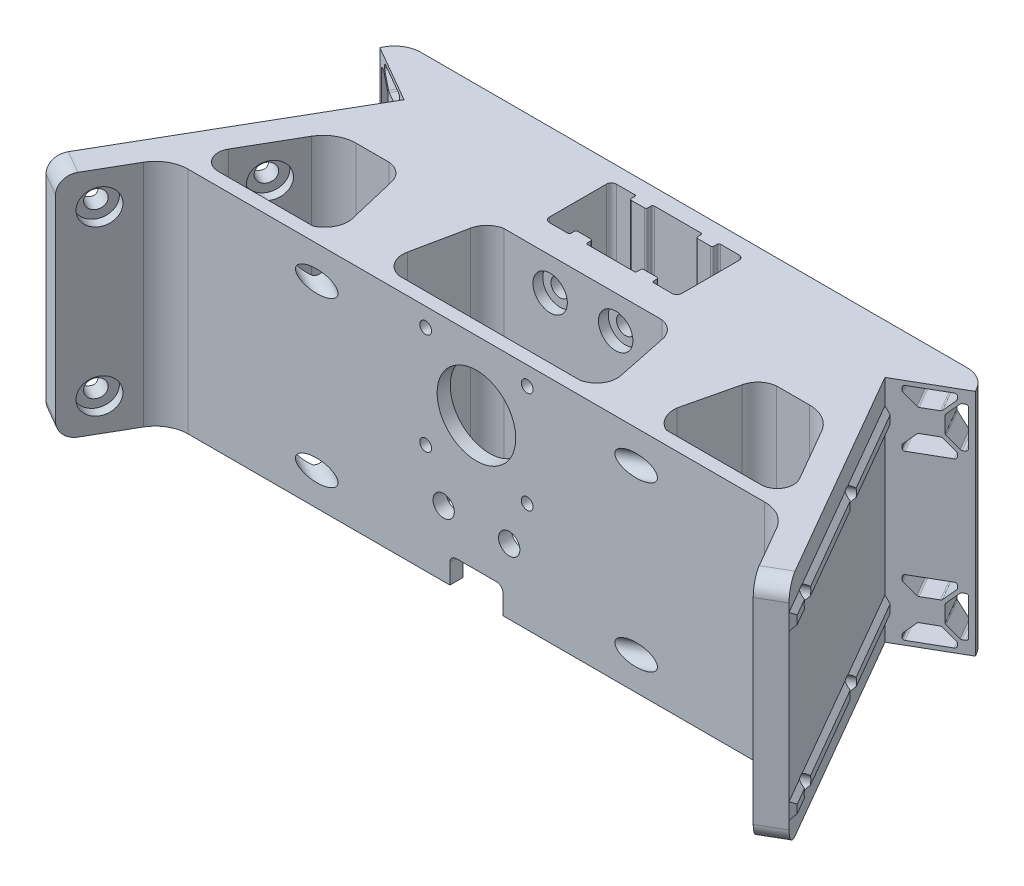
SolidWorks part; units mm, degrees
ref_plane "Front Plane" through (0, 0, 0) normal (0, 0, 1) x (1, 0, 0)
ref_plane "Top Plane" through (0, 0, 0) normal (0, 1, 0) x (1, 0, 0)
ref_plane "Right Plane" through (0, 0, 0) normal (1, 0, 0) x (0, 0, -1)
sketch "Sketch1" plane through (0, 0, 0) normal (0, 1, 0) x (1, 0, 0)
  line L0 (0, -61.4) -> (0, -111.1933) construction
  line L1 (0, 0) -> (-7.6, 0) construction
  line L2 (0, 0) -> (0, -20.4) construction
  line L3 (0, -20.4) -> (-7.1, -20.4) construction
  line L4 (-20.2, 0) -> (-20.2, -20.4) construction
  line L5 (0, 5) -> (-83.3812, 5)
  line L6 (-90.3094, 1) -> (-90.8868, 0)
  line L7 (-90.8868, 0) -> (-73.393, -10.1)
  line L8 (-73.393, -10.1) -> (-113.393, -79.382)
  line L9 (-113.393, -79.382) -> (-106.4648, -83.382)
  line L10 (-106.4648, -83.382) -> (-96.6603, -66.4)
  line L11 (-69.2361, -28.9) -> (0, -28.9)
  line L12 (0, -57.4) -> (0, -61.4)
  line L13 (0, -20.4) -> (-7.1, -20.4)
  line L14 (-20.2, -18.9) -> (-20.2, -1.5)
  line L15 (-18.7, 0) -> (-13.1, 0)
  line L16 (-82.8038, -57.4) -> (0, -57.4)
  line L17 (0, -20.4) -> (0, -28.9)
  line L18 (0, -61.4) -> (-88, -61.4)
  line L19 (-87.134, -49.9) -> (-77.8964, -33.9)
  line L20 (0, 0) -> (0, -20.4) construction
  line L21 (-7.6, -0.5) -> (-7.6, -1.5)
  line L22 (-20.2, -10.2) -> (0, -10.2) construction
  line L23 (-8.1, -2) -> (-12.1, -2)
  line L24 (-12.6, -0.5) -> (-12.6, -1.5)
  line L25 (-12.6, -19.9) -> (-12.6, -18.9)
  line L26 (-8.1, -18.4) -> (-12.1, -18.4)
  line L27 (-12.6, 0) -> (-20.2, 0) construction
  line L28 (-7.1, 0) -> (0, 0)
  line L29 (-7.6, -19.9) -> (-7.6, -18.9)
  line L30 (-13.1, -20.4) -> (-20.2, -20.4) construction
  line L31 (-13.1, -20.4) -> (-18.7, -20.4)
  line L32 (0, -28.9) -> (0, -57.4) construction
  line L33 (0, 5) -> (0, 0)
  arc A0 (-88, -61.4) -> (-96.6603, -66.4) centre (-88, -71.4) ccw
  arc A1 (-77.8964, -33.9) -> (-69.2361, -28.9) centre (-69.2361, -38.9) cw
  arc A2 (-82.8038, -57.4) -> (-87.134, -49.9) centre (-82.8038, -52.4) cw
  arc A3 (-83.3812, 5) -> (-90.3094, 1) centre (-83.3812, -3) ccw
  arc A4 (-7.1, 0) -> (-7.6, -0.5) centre (-7.1, -0.5) ccw
  arc A5 (-12.6, -0.5) -> (-13.1, 0) centre (-13.1, -0.5) ccw
  arc A6 (-7.6, -1.5) -> (-8.1, -2) centre (-8.1, -1.5) cw
  arc A7 (-12.1, -2) -> (-12.6, -1.5) centre (-12.1, -1.5) cw
  arc A8 (-20.2, -1.5) -> (-18.7, 0) centre (-18.7, -1.5) cw
  arc A9 (-18.7, -20.4) -> (-20.2, -18.9) centre (-18.7, -18.9) cw
  arc A10 (-12.1, -18.4) -> (-12.6, -18.9) centre (-12.1, -18.9) ccw
  arc A11 (-7.6, -18.9) -> (-8.1, -18.4) centre (-8.1, -18.9) ccw
  arc A12 (-12.6, -19.9) -> (-13.1, -20.4) centre (-13.1, -19.9) cw
  arc A13 (-7.1, -20.4) -> (-7.6, -19.9) centre (-7.1, -19.9) cw
  point P24 (-91.4641, -57.4)
  point P27 (-88, 5)
  point P30 (-10.1, 0)
  point P63 (-10.1, -20.4)
  dimension "D13" = 10
  dimension "D14" = 5
  dimension "D15" = 8
  dimension "D17" = 0.5
  dimension "D18" = 1.5
  dimension "D1" = 20.2
  dimension "D2" = 20.4
  dimension "D3" = 5
  dimension "D4" = 88
  dimension "D5" = 120
  dimension "D6" = 5
  dimension "D7" = 20.2
  dimension "D8" = 80
  dimension "D9" = 8
  dimension "D10" = 8.5
  dimension "D11" = 4
  dimension "D12" = 37
  dimension "D16" = 5
extrude "Boss-Extrude2" add sketch "Sketch1" along normal blind 70
sketch "Sketch2" plane through (-50.6714, 0, -29.2551) normal (-0.866, 0, -0.5) x (-0.5, 0, 0.866)
  line L0 (45.4434, 70) -> (45.4434, 0) construction
  line L1 (45.4434, 62.5) -> (125.4434, 62.5)
  line L2 (45.4434, 62.5) -> (45.4434, 57.5)
  line L3 (45.4434, 57.5) -> (125.4434, 57.5)
  line L4 (125.4434, 62.5) -> (125.4434, 57.5)
  line L5 (125.4434, 70) -> (125.4434, 0) construction
  line L6 (45.4434, 70) -> (125.4434, 70) construction
  line L7 (45.4434, 35) -> (125.4434, 35) construction
  line L8 (125.4434, 7.5) -> (125.4434, 12.5)
  line L9 (45.4434, 12.5) -> (125.4434, 12.5)
  line L10 (45.4434, 7.5) -> (45.4434, 12.5)
  line L11 (45.4434, 7.5) -> (125.4434, 7.5)
  dimension "D1" = 5
  dimension "D2" = 7.5
extrude "Boss-Extrude3" add sketch "Sketch2" along normal blind 1.5 draft 40
hole_wizard "CBORE for M5 SHCS2" positions "Sketch5" profile "Sketch4" counterbore size "M5" standard "ANSI Metric" end condition up to next
sketch "Sketch5" plane through (-43.7431, 0, -25.2551) normal (0.866, 0, 0.5) x (0.5, 0, -0.866)
  line L0 (-125.4434, 60) -> (-68.3064, 60) construction
  line L1 (-125.4434, 70) -> (-125.4434, 0) construction
  line L2 (-68.3064, 70) -> (-68.3064, 0) construction
  line L4 (-86.7817, 70) -> (-68.3064, 70) construction
  line L5 (-125.4434, 10) -> (-68.3064, 10) construction
  line L7 (-125.4434, 0) -> (-105.8342, 0) construction
  line L10 (-125.4434, 70) -> (-105.8342, 70) construction
  line L11 (-115.6388, 70) -> (-115.6388, 60) construction
  line L13 (-77.5441, 70) -> (-77.5441, 60) construction
  point P0 (-77.5441, 60)
  point P2 (-77.5441, 10)
  point P4 (-115.6388, 60)
  point P6 (-115.6388, 10)
  dimension "D1" = 10
  dimension "D2" = 10
sketch "Sketch4" plane through (-82.5152, 60, 41.9) normal (0, 1, 0) x (0.5, 0, -0.866)
  line L0 (0, 0) -> (0, 9.5)
  line L1 (0, 9.5) -> (2.75, 9.5)
  line L3 (2.75, 9.5) -> (2.75, 3)
  line L4 (2.75, 3) -> (5.25, 3)
  line L5 (5.25, 3) -> (5.25, 0)
  line L7 (5.25, 0) -> (0, 0)
  line L11 (0, -6.35) -> (0, 107.95) construction
  dimension "Thru Hole Dia." = 5.5
  dimension "Thru Hole Depth" = 9.5
  dimension "C'Bore Dia." = 10.5
  dimension "C'Bore Depth" = 3
hole_wizard "CBORE for M5 SHCS3" positions "Sketch7" profile "Sketch6" counterbore size "M5" standard "ANSI Metric" end condition up to next
sketch "Sketch7" plane through (0, 0, 28.9) normal (0, 0, 1) x (1, 0, 0)
  line L0 (0, 60) -> (0, 0) construction
  line L1 (-69.2361, 70) -> (0, 70) construction
  line L2 (-69.2361, 0) -> (0, 0) construction
  line L4 (0, 60) -> (-28.3411, 60)
  line L6 (0, 20) -> (-25.3792, 20) construction
  line L8 (-69.2361, 0) -> (0, 0) construction
  line L10 (0, 70) -> (0, 0) construction
  point P0 (-10, 20)
  point P2 (-10, 60)
  dimension "D1" = 10
  dimension "D2" = 10
  dimension "D3" = 20
sketch "Sketch6" plane through (-10, 20, 28.9) normal (1, 0, 0) x (0, -1, 0)
  line L0 (0, 0) -> (0, 10.5)
  line L1 (0, 10.5) -> (2.75, 10.5)
  line L3 (2.75, 10.5) -> (2.75, 3)
  line L4 (2.75, 3) -> (5.25, 3)
  line L5 (5.25, 3) -> (5.25, 0)
  line L7 (5.25, 0) -> (0, 0)
  line L11 (0, -6.35) -> (0, 107.95) construction
  dimension "Thru Hole Dia." = 5.5
  dimension "Thru Hole Depth" = 10.5
  dimension "C'Bore Dia." = 10.5
  dimension "C'Bore Depth" = 3
chamfer "Chamfer1" [suppressed] distance 5 angle 45
chamfer "Chamfer2" [suppressed] distance 5 angle 45
fillet "Fillet1" radius 5 2 edges at (-109.9289, 0, 81.382) (-109.9289, 70, 81.382)
sketch "Sketch14" plane through (-22.7217, 0, 39.3551) normal (-0.5, 0, 0.866) x (0.866, 0, 0.5)
  line L0 (-73.9972, 68.5) -> (-63.0232, 68.5)
  line L1 (-62.5152, 67.992) -> (-62.5152, 67.2661)
  line L2 (-65.7671, 63.8038) -> (-62.664, 66.9069)
  line L3 (-66.1263, 63.655) -> (-70.8942, 63.655)
  line L12 (-74.5052, 67.992) -> (-74.5052, 67.2661)
  line L13 (-74.3564, 66.9069) -> (-71.2534, 63.8038)
  line L14 (-77.0102, 65.487) -> (-77.0102, 54.513)
  line L15 (-76.5022, 54.005) -> (-75.7763, 54.005)
  line L16 (-75.4171, 54.1538) -> (-72.314, 57.2569)
  line L17 (-72.1652, 57.6161) -> (-72.1652, 62.3839)
  line L18 (-72.314, 62.7431) -> (-75.4171, 65.8462)
  line L19 (-75.7763, 65.995) -> (-76.5022, 65.995)
  line L20 (-73.9972, 51.5) -> (-63.0232, 51.5)
  line L21 (-62.5152, 52.008) -> (-62.5152, 52.7339)
  line L22 (-62.664, 53.0931) -> (-65.7671, 56.1962)
  line L23 (-66.1263, 56.345) -> (-70.8942, 56.345)
  line L25 (-71.2534, 56.1962) -> (-74.3564, 53.0931)
  line L26 (-74.5052, 52.7339) -> (-74.5052, 52.008)
  line L52 (-74.5052, 52.008) -> (-74.5052, 52.7339)
  line L53 (-71.6482, 51.5) -> (-73.9972, 51.5)
  line L54 (-71.1402, 50.508) -> (-71.1402, 50.992)
  line L55 (-77.0102, 50) -> (-71.6482, 50)
  line L56 (-78.5102, 56.862) -> (-78.5102, 51.5)
  line L57 (-77.5182, 57.37) -> (-78.0022, 57.37)
  line L58 (-77.0102, 54.513) -> (-77.0102, 56.862)
  line L59 (-75.7763, 54.005) -> (-76.5022, 54.005)
  line L60 (-72.314, 57.2569) -> (-75.4171, 54.1538)
  line L61 (-72.1652, 62.3839) -> (-72.1652, 57.6161)
  line L62 (-75.4171, 65.8462) -> (-72.314, 62.7431)
  line L63 (-76.5022, 65.995) -> (-75.7763, 65.995)
  line L64 (-77.0102, 63.138) -> (-77.0102, 65.487)
  line L65 (-78.0022, 62.63) -> (-77.5182, 62.63)
  line L66 (-78.5102, 68.5) -> (-78.5102, 63.138)
  line L67 (-71.6482, 70) -> (-77.0102, 70)
  line L68 (-71.1402, 69.008) -> (-71.1402, 69.492)
  line L69 (-73.9972, 68.5) -> (-71.6482, 68.5)
  line L70 (-74.5052, 67.2661) -> (-74.5052, 67.992)
  line L71 (-71.2534, 63.8038) -> (-74.3564, 66.9069)
  line L72 (-66.1263, 63.655) -> (-70.8942, 63.655)
  line L73 (-62.664, 66.9069) -> (-65.7671, 63.8038)
  line L74 (-62.5152, 67.992) -> (-62.5152, 67.2661)
  line L75 (-65.3722, 68.5) -> (-63.0232, 68.5)
  line L76 (-65.8802, 69.492) -> (-65.8802, 69.008)
  line L77 (-60.0102, 70) -> (-65.3722, 70)
  line L78 (-58.5102, 63.138) -> (-58.5102, 68.5)
  line L79 (-59.5022, 62.63) -> (-59.0182, 62.63)
  line L80 (-60.0102, 65.487) -> (-60.0102, 63.138)
  line L81 (-61.2442, 65.995) -> (-60.5182, 65.995)
  line L82 (-64.7064, 62.7431) -> (-61.6034, 65.8462)
  line L83 (-64.8552, 57.6161) -> (-64.8552, 62.3839)
  line L84 (-61.6034, 54.1538) -> (-64.7064, 57.2569)
  line L85 (-60.5182, 54.005) -> (-61.2442, 54.005)
  line L86 (-60.0102, 56.862) -> (-60.0102, 54.513)
  line L87 (-59.0182, 57.37) -> (-59.5022, 57.37)
  line L88 (-58.5102, 51.5) -> (-58.5102, 56.862)
  line L89 (-65.3722, 50) -> (-60.0102, 50)
  line L90 (-65.8802, 50.992) -> (-65.8802, 50.508)
  line L91 (-63.0232, 51.5) -> (-65.3722, 51.5)
  line L92 (-62.5152, 52.7339) -> (-62.5152, 52.008)
  line L93 (-65.7671, 56.1962) -> (-62.664, 53.0931)
  line L94 (-70.8942, 56.345) -> (-66.1263, 56.345)
  line L95 (-74.3564, 53.0931) -> (-71.2534, 56.1962)
  line L96 (-74.5052, 52.008) -> (-74.5052, 52.7339) construction
  line L97 (-71.6482, 51.5) -> (-73.9972, 51.5) construction
  line L98 (-71.1402, 50.508) -> (-71.1402, 50.992) construction
  line L99 (-77.0102, 50) -> (-71.6482, 50) construction
  line L100 (-78.5102, 56.862) -> (-78.5102, 51.5) construction
  line L101 (-77.5182, 57.37) -> (-78.0022, 57.37) construction
  line L102 (-77.0102, 54.513) -> (-77.0102, 56.862) construction
  line L103 (-75.7763, 54.005) -> (-76.5022, 54.005) construction
  line L104 (-72.314, 57.2569) -> (-75.4171, 54.1538) construction
  line L105 (-72.1652, 62.3839) -> (-72.1652, 57.6161) construction
  line L106 (-75.4171, 65.8462) -> (-72.314, 62.7431) construction
  line L107 (-76.5022, 65.995) -> (-75.7763, 65.995) construction
  line L108 (-77.0102, 63.138) -> (-77.0102, 65.487) construction
  line L109 (-78.0022, 62.63) -> (-77.5182, 62.63) construction
  line L110 (-78.5102, 68.5) -> (-78.5102, 63.138) construction
  line L111 (-71.6482, 70) -> (-77.0102, 70) construction
  line L112 (-71.1402, 69.008) -> (-71.1402, 69.492) construction
  line L113 (-73.9972, 68.5) -> (-71.6482, 68.5) construction
  line L114 (-74.5052, 67.2661) -> (-74.5052, 67.992) construction
  line L115 (-71.2534, 63.8038) -> (-74.3564, 66.9069) construction
  line L116 (-66.1263, 63.655) -> (-70.8942, 63.655) construction
  line L117 (-62.664, 66.9069) -> (-65.7671, 63.8038) construction
  line L118 (-62.5152, 67.992) -> (-62.5152, 67.2661) construction
  line L119 (-65.3722, 68.5) -> (-63.0232, 68.5) construction
  line L120 (-65.8802, 69.492) -> (-65.8802, 69.008) construction
  line L121 (-60.0102, 70) -> (-65.3722, 70) construction
  line L122 (-58.5102, 63.138) -> (-58.5102, 68.5) construction
  line L123 (-59.5022, 62.63) -> (-59.0182, 62.63) construction
  line L124 (-60.0102, 65.487) -> (-60.0102, 63.138) construction
  line L125 (-61.2442, 65.995) -> (-60.5182, 65.995) construction
  line L126 (-64.7064, 62.7431) -> (-61.6034, 65.8462) construction
  line L127 (-64.8552, 57.6161) -> (-64.8552, 62.3839) construction
  line L128 (-61.6034, 54.1538) -> (-64.7064, 57.2569) construction
  line L129 (-60.5182, 54.005) -> (-61.2442, 54.005) construction
  line L130 (-60.0102, 56.862) -> (-60.0102, 54.513) construction
  line L131 (-59.0182, 57.37) -> (-59.5022, 57.37) construction
  line L132 (-58.5102, 51.5) -> (-58.5102, 56.862) construction
  line L133 (-65.3722, 50) -> (-60.0102, 50) construction
  line L134 (-65.8802, 50.992) -> (-65.8802, 50.508) construction
  line L135 (-63.0232, 51.5) -> (-65.3722, 51.5) construction
  line L136 (-62.5152, 52.7339) -> (-62.5152, 52.008) construction
  line L137 (-65.7671, 56.1962) -> (-62.664, 53.0931) construction
  line L138 (-70.8942, 56.345) -> (-66.1263, 56.345) construction
  line L139 (-74.3564, 53.0931) -> (-71.2534, 56.1962) construction
  arc A0 (-74.5052, 67.992) -> (-73.9972, 68.5) centre (-73.9972, 67.992) cw
  arc A1 (-74.3564, 66.9069) -> (-74.5052, 67.2661) centre (-73.9972, 67.2661) cw
  arc A2 (-71.2534, 63.8038) -> (-70.8942, 63.655) centre (-70.8942, 64.163) ccw
  arc A3 (-66.1263, 63.655) -> (-65.7671, 63.8038) centre (-66.1263, 64.163) ccw
  arc A4 (-62.664, 66.9069) -> (-62.5152, 67.2661) centre (-63.0232, 67.2661) ccw
  arc A5 (-62.5152, 67.992) -> (-63.0232, 68.5) centre (-63.0232, 67.992) ccw
  arc A6 (-77.0102, 54.513) -> (-76.5022, 54.005) centre (-76.5022, 54.513) ccw
  arc A7 (-75.7763, 54.005) -> (-75.4171, 54.1538) centre (-75.7763, 54.513) ccw
  arc A8 (-72.314, 57.2569) -> (-72.1652, 57.6161) centre (-72.6732, 57.6161) ccw
  arc A9 (-72.1652, 62.3839) -> (-72.314, 62.7431) centre (-72.6732, 62.3839) ccw
  arc A10 (-75.4171, 65.8462) -> (-75.7763, 65.995) centre (-75.7763, 65.487) ccw
  arc A11 (-76.5022, 65.995) -> (-77.0102, 65.487) centre (-76.5022, 65.487) ccw
  arc A36 (-63.0232, 51.5) -> (-62.5152, 52.008) centre (-63.0232, 52.008) ccw
  arc A37 (-62.5152, 52.7339) -> (-62.664, 53.0931) centre (-63.0232, 52.7339) ccw
  arc A38 (-65.7671, 56.1962) -> (-66.1263, 56.345) centre (-66.1263, 55.837) ccw
  arc A39 (-74.3564, 53.0931) -> (-74.5052, 52.7339) centre (-73.9972, 52.7339) ccw
  arc A40 (-74.5052, 52.008) -> (-73.9972, 51.5) centre (-73.9972, 52.008) ccw
  arc A41 (-70.8942, 56.345) -> (-71.2534, 56.1962) centre (-70.8942, 55.837) ccw
  arc A68 (-74.5052, 52.008) -> (-73.9972, 51.5) centre (-73.9972, 52.008) ccw
  arc A69 (-71.1402, 50.992) -> (-71.6482, 51.5) centre (-71.6482, 50.992) ccw
  arc A70 (-71.6482, 50) -> (-71.1402, 50.508) centre (-71.6482, 50.508) ccw
  arc A71 (-78.5102, 51.5) -> (-77.0102, 50) centre (-77.0102, 51.5) ccw
  arc A72 (-78.0022, 57.37) -> (-78.5102, 56.862) centre (-78.0022, 56.862) ccw
  arc A73 (-77.0102, 56.862) -> (-77.5182, 57.37) centre (-77.5182, 56.862) ccw
  arc A74 (-77.0102, 54.513) -> (-76.5022, 54.005) centre (-76.5022, 54.513) ccw
  arc A75 (-75.7763, 54.005) -> (-75.4171, 54.1538) centre (-75.7763, 54.513) ccw
  arc A76 (-72.314, 57.2569) -> (-72.1652, 57.6161) centre (-72.6732, 57.6161) ccw
  arc A77 (-72.1652, 62.3839) -> (-72.314, 62.7431) centre (-72.6732, 62.3839) ccw
  arc A78 (-75.4171, 65.8462) -> (-75.7763, 65.995) centre (-75.7763, 65.487) ccw
  arc A79 (-76.5022, 65.995) -> (-77.0102, 65.487) centre (-76.5022, 65.487) ccw
  arc A80 (-77.5182, 62.63) -> (-77.0102, 63.138) centre (-77.5182, 63.138) ccw
  arc A81 (-78.5102, 63.138) -> (-78.0022, 62.63) centre (-78.0022, 63.138) ccw
  arc A82 (-77.0102, 70) -> (-78.5102, 68.5) centre (-77.0102, 68.5) ccw
  arc A83 (-71.1402, 69.492) -> (-71.6482, 70) centre (-71.6482, 69.492) ccw
  arc A84 (-71.6482, 68.5) -> (-71.1402, 69.008) centre (-71.6482, 69.008) ccw
  arc A85 (-73.9972, 68.5) -> (-74.5052, 67.992) centre (-73.9972, 67.992) ccw
  arc A86 (-74.5052, 67.2661) -> (-74.3564, 66.9069) centre (-73.9972, 67.2661) ccw
  arc A87 (-71.2534, 63.8038) -> (-70.8942, 63.655) centre (-70.8942, 64.163) ccw
  arc A88 (-66.1263, 63.655) -> (-65.7671, 63.8038) centre (-66.1263, 64.163) ccw
  arc A89 (-62.664, 66.9069) -> (-62.5152, 67.2661) centre (-63.0232, 67.2661) ccw
  arc A90 (-62.5152, 67.992) -> (-63.0232, 68.5) centre (-63.0232, 67.992) ccw
  arc A91 (-65.8802, 69.008) -> (-65.3722, 68.5) centre (-65.3722, 69.008) ccw
  arc A92 (-65.3722, 70) -> (-65.8802, 69.492) centre (-65.3722, 69.492) ccw
  arc A93 (-58.5102, 68.5) -> (-60.0102, 70) centre (-60.0102, 68.5) ccw
  arc A94 (-59.0182, 62.63) -> (-58.5102, 63.138) centre (-59.0182, 63.138) ccw
  arc A95 (-60.0102, 63.138) -> (-59.5022, 62.63) centre (-59.5022, 63.138) ccw
  arc A96 (-60.0102, 65.487) -> (-60.5182, 65.995) centre (-60.5182, 65.487) ccw
  arc A97 (-61.2442, 65.995) -> (-61.6034, 65.8462) centre (-61.2442, 65.487) ccw
  arc A98 (-64.7064, 62.7431) -> (-64.8552, 62.3839) centre (-64.3472, 62.3839) ccw
  arc A99 (-64.8552, 57.6161) -> (-64.7064, 57.2569) centre (-64.3472, 57.6161) ccw
  arc A100 (-61.6034, 54.1538) -> (-61.2442, 54.005) centre (-61.2442, 54.513) ccw
  arc A101 (-60.5182, 54.005) -> (-60.0102, 54.513) centre (-60.5182, 54.513) ccw
  arc A102 (-59.5022, 57.37) -> (-60.0102, 56.862) centre (-59.5022, 56.862) ccw
  arc A103 (-58.5102, 56.862) -> (-59.0182, 57.37) centre (-59.0182, 56.862) ccw
  arc A104 (-60.0102, 50) -> (-58.5102, 51.5) centre (-60.0102, 51.5) ccw
  arc A105 (-65.8802, 50.508) -> (-65.3722, 50) centre (-65.3722, 50.508) ccw
  arc A106 (-65.3722, 51.5) -> (-65.8802, 50.992) centre (-65.3722, 50.992) ccw
  arc A107 (-63.0232, 51.5) -> (-62.5152, 52.008) centre (-63.0232, 52.008) ccw
  arc A108 (-62.5152, 52.7339) -> (-62.664, 53.0931) centre (-63.0232, 52.7339) ccw
  arc A109 (-65.7671, 56.1962) -> (-66.1263, 56.345) centre (-66.1263, 55.837) ccw
  arc A110 (-70.8942, 56.345) -> (-71.2534, 56.1962) centre (-70.8942, 55.837) ccw
  arc A111 (-74.3564, 53.0931) -> (-74.5052, 52.7339) centre (-73.9972, 52.7339) ccw
  arc A112 (-74.5052, 52.008) -> (-73.9972, 51.5) centre (-73.9972, 52.008) ccw construction
  arc A113 (-71.1402, 50.992) -> (-71.6482, 51.5) centre (-71.6482, 50.992) ccw construction
  arc A114 (-71.6482, 50) -> (-71.1402, 50.508) centre (-71.6482, 50.508) ccw construction
  arc A115 (-78.5102, 51.5) -> (-77.0102, 50) centre (-77.0102, 51.5) ccw construction
  arc A116 (-78.0022, 57.37) -> (-78.5102, 56.862) centre (-78.0022, 56.862) ccw construction
  arc A117 (-77.0102, 56.862) -> (-77.5182, 57.37) centre (-77.5182, 56.862) ccw construction
  arc A118 (-77.0102, 54.513) -> (-76.5022, 54.005) centre (-76.5022, 54.513) ccw construction
  arc A119 (-75.7763, 54.005) -> (-75.4171, 54.1538) centre (-75.7763, 54.513) ccw construction
  arc A120 (-72.314, 57.2569) -> (-72.1652, 57.6161) centre (-72.6732, 57.6161) ccw construction
  arc A121 (-72.1652, 62.3839) -> (-72.314, 62.7431) centre (-72.6732, 62.3839) ccw construction
  arc A122 (-75.4171, 65.8462) -> (-75.7763, 65.995) centre (-75.7763, 65.487) ccw construction
  arc A123 (-76.5022, 65.995) -> (-77.0102, 65.487) centre (-76.5022, 65.487) ccw construction
  arc A124 (-77.5182, 62.63) -> (-77.0102, 63.138) centre (-77.5182, 63.138) ccw construction
  arc A125 (-78.5102, 63.138) -> (-78.0022, 62.63) centre (-78.0022, 63.138) ccw construction
  arc A126 (-77.0102, 70) -> (-78.5102, 68.5) centre (-77.0102, 68.5) ccw construction
  arc A127 (-71.1402, 69.492) -> (-71.6482, 70) centre (-71.6482, 69.492) ccw construction
  arc A128 (-71.6482, 68.5) -> (-71.1402, 69.008) centre (-71.6482, 69.008) ccw construction
  arc A129 (-73.9972, 68.5) -> (-74.5052, 67.992) centre (-73.9972, 67.992) ccw construction
  arc A130 (-74.5052, 67.2661) -> (-74.3564, 66.9069) centre (-73.9972, 67.2661) ccw construction
  arc A131 (-71.2534, 63.8038) -> (-70.8942, 63.655) centre (-70.8942, 64.163) ccw construction
  arc A132 (-66.1263, 63.655) -> (-65.7671, 63.8038) centre (-66.1263, 64.163) ccw construction
  arc A133 (-62.664, 66.9069) -> (-62.5152, 67.2661) centre (-63.0232, 67.2661) ccw construction
  arc A134 (-62.5152, 67.992) -> (-63.0232, 68.5) centre (-63.0232, 67.992) ccw construction
  arc A135 (-65.8802, 69.008) -> (-65.3722, 68.5) centre (-65.3722, 69.008) ccw construction
  arc A136 (-65.3722, 70) -> (-65.8802, 69.492) centre (-65.3722, 69.492) ccw construction
  arc A137 (-58.5102, 68.5) -> (-60.0102, 70) centre (-60.0102, 68.5) ccw construction
  arc A138 (-59.0182, 62.63) -> (-58.5102, 63.138) centre (-59.0182, 63.138) ccw construction
  arc A139 (-60.0102, 63.138) -> (-59.5022, 62.63) centre (-59.5022, 63.138) ccw construction
  arc A140 (-60.0102, 65.487) -> (-60.5182, 65.995) centre (-60.5182, 65.487) ccw construction
  arc A141 (-61.2442, 65.995) -> (-61.6034, 65.8462) centre (-61.2442, 65.487) ccw construction
  arc A142 (-64.7064, 62.7431) -> (-64.8552, 62.3839) centre (-64.3472, 62.3839) ccw construction
  arc A143 (-64.8552, 57.6161) -> (-64.7064, 57.2569) centre (-64.3472, 57.6161) ccw construction
  arc A144 (-61.6034, 54.1538) -> (-61.2442, 54.005) centre (-61.2442, 54.513) ccw construction
  arc A145 (-60.5182, 54.005) -> (-60.0102, 54.513) centre (-60.5182, 54.513) ccw construction
  arc A146 (-59.5022, 57.37) -> (-60.0102, 56.862) centre (-59.5022, 56.862) ccw construction
  arc A147 (-58.5102, 56.862) -> (-59.0182, 57.37) centre (-59.0182, 56.862) ccw construction
  arc A148 (-60.0102, 50) -> (-58.5102, 51.5) centre (-60.0102, 51.5) ccw construction
  arc A149 (-65.8802, 50.508) -> (-65.3722, 50) centre (-65.3722, 50.508) ccw construction
  arc A150 (-65.3722, 51.5) -> (-65.8802, 50.992) centre (-65.3722, 50.992) ccw construction
  arc A151 (-63.0232, 51.5) -> (-62.5152, 52.008) centre (-63.0232, 52.008) ccw construction
  arc A152 (-62.5152, 52.7339) -> (-62.664, 53.0931) centre (-63.0232, 52.7339) ccw construction
  arc A153 (-65.7671, 56.1962) -> (-66.1263, 56.345) centre (-66.1263, 55.837) ccw construction
  arc A154 (-70.8942, 56.345) -> (-71.2534, 56.1962) centre (-70.8942, 55.837) ccw construction
  arc A155 (-74.3564, 53.0931) -> (-74.5052, 52.7339) centre (-73.9972, 52.7339) ccw construction
  dimension "D2" = 0
sketch "Sketch15" plane through (-22.7217, 0, 39.3551) normal (-0.5, 0, 0.866) x (0.866, 0, 0.5)
  line L0 (-77.2102, 65.487) -> (-77.2102, 54.513)
  line L1 (-76.5022, 53.805) -> (-75.7763, 53.805)
  line L2 (-75.2757, 54.0124) -> (-72.1726, 57.1154)
  line L3 (-71.9652, 57.6161) -> (-71.9652, 62.3839)
  line L4 (-72.1726, 62.8846) -> (-75.2757, 65.9876)
  line L5 (-75.7763, 66.195) -> (-76.5022, 66.195)
  line L6 (-77.0102, 65.487) -> (-77.0102, 54.513)
  line L7 (-76.5022, 54.005) -> (-75.7763, 54.005)
  line L8 (-75.4171, 54.1538) -> (-72.314, 57.2569)
  line L9 (-72.1652, 57.6161) -> (-72.1652, 62.3839)
  line L10 (-72.314, 62.7431) -> (-75.4171, 65.8462)
  line L11 (-75.7763, 65.995) -> (-76.5022, 65.995)
  line L12 (-77.0102, 65.487) -> (-77.0102, 54.513) construction
  line L13 (-76.5022, 54.005) -> (-75.7763, 54.005) construction
  line L14 (-75.4171, 54.1538) -> (-72.314, 57.2569) construction
  line L15 (-72.1652, 57.6161) -> (-72.1652, 62.3839) construction
  line L16 (-72.314, 62.7431) -> (-75.4171, 65.8462) construction
  line L17 (-75.7763, 65.995) -> (-76.5022, 65.995) construction
  line L18 (-63.0232, 68.5) -> (-73.9972, 68.5)
  line L19 (-74.5052, 67.992) -> (-74.5052, 67.2661)
  line L20 (-74.3564, 66.9069) -> (-71.2534, 63.8038)
  line L21 (-70.8942, 63.655) -> (-66.1263, 63.655)
  line L22 (-65.7671, 63.8038) -> (-62.664, 66.9069)
  line L23 (-62.5152, 67.2661) -> (-62.5152, 67.992)
  line L24 (-63.0232, 68.5) -> (-73.9972, 68.5) construction
  line L25 (-74.5052, 67.992) -> (-74.5052, 67.2661) construction
  line L26 (-74.3564, 66.9069) -> (-71.2534, 63.8038) construction
  line L27 (-70.8942, 63.655) -> (-66.1263, 63.655) construction
  line L28 (-65.7671, 63.8038) -> (-62.664, 66.9069) construction
  line L29 (-62.5152, 67.2661) -> (-62.5152, 67.992) construction
  line L30 (-73.9972, 51.5) -> (-63.0232, 51.5)
  line L31 (-74.5052, 52.7339) -> (-74.5052, 52.008)
  line L32 (-71.2534, 56.1962) -> (-74.3564, 53.0931)
  line L33 (-66.1263, 56.345) -> (-70.8942, 56.345)
  line L34 (-62.664, 53.0931) -> (-65.7671, 56.1962)
  line L35 (-62.5152, 52.008) -> (-62.5152, 52.7339)
  line L36 (-73.9972, 51.5) -> (-63.0232, 51.5) construction
  line L37 (-74.5052, 52.7339) -> (-74.5052, 52.008) construction
  line L38 (-71.2534, 56.1962) -> (-74.3564, 53.0931) construction
  line L39 (-66.1263, 56.345) -> (-70.8942, 56.345) construction
  line L40 (-62.664, 53.0931) -> (-65.7671, 56.1962) construction
  line L41 (-62.5152, 52.008) -> (-62.5152, 52.7339) construction
  line L42 (-63.0232, 68.7) -> (-73.9972, 68.7)
  line L43 (-74.7052, 67.992) -> (-74.7052, 67.2661)
  line L44 (-74.4979, 66.7654) -> (-71.3948, 63.6624)
  line L45 (-70.8942, 63.455) -> (-66.1263, 63.455)
  line L46 (-65.6257, 63.6624) -> (-62.5226, 66.7654)
  line L47 (-62.3152, 67.2661) -> (-62.3152, 67.992)
  line L48 (-73.9972, 51.3) -> (-63.0232, 51.3)
  line L49 (-62.3152, 52.008) -> (-62.3152, 52.7339)
  line L50 (-62.5226, 53.2346) -> (-65.6257, 56.3376)
  line L51 (-66.1263, 56.545) -> (-70.8942, 56.545)
  line L52 (-71.3948, 56.3376) -> (-74.4979, 53.2346)
  line L53 (-74.7052, 52.7339) -> (-74.7052, 52.008)
  line L54 (-58.5102, 35) -> (-78.7102, 35) construction
  line L55 (-58.5102, 57.5) -> (-58.5102, 12.5) construction
  line L56 (-78.7102, 70) -> (-78.7102, 0) construction
  line L57 (-62.5152, 17.992) -> (-62.5152, 17.2661) construction
  line L58 (-62.664, 16.9069) -> (-65.7671, 13.8038) construction
  line L59 (-66.1263, 13.655) -> (-70.8942, 13.655) construction
  line L60 (-71.2534, 13.8038) -> (-74.3564, 16.9069) construction
  line L61 (-74.5052, 17.2661) -> (-74.5052, 17.992) construction
  line L62 (-73.9972, 18.5) -> (-63.0232, 18.5) construction
  line L63 (-62.5152, 2.7339) -> (-62.5152, 2.008) construction
  line L64 (-65.7671, 6.1962) -> (-62.664, 3.0931) construction
  line L65 (-70.8942, 6.345) -> (-66.1263, 6.345) construction
  line L66 (-74.3564, 3.0931) -> (-71.2534, 6.1962) construction
  line L67 (-74.5052, 2.008) -> (-74.5052, 2.7339) construction
  line L68 (-63.0232, 1.5) -> (-73.9972, 1.5) construction
  line L69 (-75.7763, 4.005) -> (-76.5022, 4.005) construction
  line L70 (-72.314, 7.2569) -> (-75.4171, 4.1538) construction
  line L71 (-72.1652, 12.3839) -> (-72.1652, 7.6161) construction
  line L72 (-75.4171, 15.8462) -> (-72.314, 12.7431) construction
  line L73 (-76.5022, 15.995) -> (-75.7763, 15.995) construction
  line L74 (-77.0102, 4.513) -> (-77.0102, 15.487) construction
  line L75 (-74.7052, 17.2661) -> (-74.7052, 17.992)
  line L76 (-71.3948, 13.6624) -> (-74.4979, 16.7654)
  line L77 (-66.1263, 13.455) -> (-70.8942, 13.455)
  line L78 (-62.5226, 16.7654) -> (-65.6257, 13.6624)
  line L79 (-62.3152, 17.992) -> (-62.3152, 17.2661)
  line L80 (-73.9972, 18.7) -> (-63.0232, 18.7)
  line L81 (-62.3152, 2.7339) -> (-62.3152, 2.008)
  line L82 (-65.6257, 6.3376) -> (-62.5226, 3.2346)
  line L83 (-70.8942, 6.545) -> (-66.1263, 6.545)
  line L84 (-74.4979, 3.2346) -> (-71.3948, 6.3376)
  line L85 (-74.7052, 2.008) -> (-74.7052, 2.7339)
  line L86 (-63.0232, 1.3) -> (-73.9972, 1.3)
  line L87 (-75.7763, 3.805) -> (-76.5022, 3.805)
  line L88 (-72.1726, 7.1154) -> (-75.2757, 4.0124)
  line L89 (-71.9652, 12.3839) -> (-71.9652, 7.6161)
  line L90 (-75.2757, 15.9876) -> (-72.1726, 12.8846)
  line L91 (-76.5022, 16.195) -> (-75.7763, 16.195)
  line L92 (-77.2102, 4.513) -> (-77.2102, 15.487)
  arc A0 (-77.2102, 54.513) -> (-76.5022, 53.805) centre (-76.5022, 54.513) ccw
  arc A1 (-75.7763, 53.805) -> (-75.2757, 54.0124) centre (-75.7763, 54.513) ccw
  arc A2 (-72.1726, 57.1154) -> (-71.9652, 57.6161) centre (-72.6732, 57.6161) ccw
  arc A3 (-71.9652, 62.3839) -> (-72.1726, 62.8846) centre (-72.6732, 62.3839) ccw
  arc A4 (-75.2757, 65.9876) -> (-75.7763, 66.195) centre (-75.7763, 65.487) ccw
  arc A5 (-76.5022, 66.195) -> (-77.2102, 65.487) centre (-76.5022, 65.487) ccw
  arc A6 (-77.0102, 54.513) -> (-76.5022, 54.005) centre (-76.5022, 54.513) ccw
  arc A7 (-75.7763, 54.005) -> (-75.4171, 54.1538) centre (-75.7763, 54.513) ccw
  arc A8 (-72.314, 57.2569) -> (-72.1652, 57.6161) centre (-72.6732, 57.6161) ccw
  arc A9 (-72.1652, 62.3839) -> (-72.314, 62.7431) centre (-72.6732, 62.3839) ccw
  arc A10 (-75.4171, 65.8462) -> (-75.7763, 65.995) centre (-75.7763, 65.487) ccw
  arc A11 (-76.5022, 65.995) -> (-77.0102, 65.487) centre (-76.5022, 65.487) ccw
  arc A12 (-77.0102, 54.513) -> (-76.5022, 54.005) centre (-76.5022, 54.513) ccw construction
  arc A13 (-75.7763, 54.005) -> (-75.4171, 54.1538) centre (-75.7763, 54.513) ccw construction
  arc A14 (-72.314, 57.2569) -> (-72.1652, 57.6161) centre (-72.6732, 57.6161) ccw construction
  arc A15 (-72.1652, 62.3839) -> (-72.314, 62.7431) centre (-72.6732, 62.3839) ccw construction
  arc A16 (-75.4171, 65.8462) -> (-75.7763, 65.995) centre (-75.7763, 65.487) ccw construction
  arc A17 (-76.5022, 65.995) -> (-77.0102, 65.487) centre (-76.5022, 65.487) ccw construction
  arc A18 (-73.9972, 68.5) -> (-74.5052, 67.992) centre (-73.9972, 67.992) ccw
  arc A19 (-74.5052, 67.2661) -> (-74.3564, 66.9069) centre (-73.9972, 67.2661) ccw
  arc A20 (-71.2534, 63.8038) -> (-70.8942, 63.655) centre (-70.8942, 64.163) ccw
  arc A21 (-66.1263, 63.655) -> (-65.7671, 63.8038) centre (-66.1263, 64.163) ccw
  arc A22 (-62.664, 66.9069) -> (-62.5152, 67.2661) centre (-63.0232, 67.2661) ccw
  arc A23 (-62.5152, 67.992) -> (-63.0232, 68.5) centre (-63.0232, 67.992) ccw
  arc A24 (-73.9972, 68.5) -> (-74.5052, 67.992) centre (-73.9972, 67.992) ccw construction
  arc A25 (-74.5052, 67.2661) -> (-74.3564, 66.9069) centre (-73.9972, 67.2661) ccw construction
  arc A26 (-71.2534, 63.8038) -> (-70.8942, 63.655) centre (-70.8942, 64.163) ccw construction
  arc A27 (-66.1263, 63.655) -> (-65.7671, 63.8038) centre (-66.1263, 64.163) ccw construction
  arc A28 (-62.664, 66.9069) -> (-62.5152, 67.2661) centre (-63.0232, 67.2661) ccw construction
  arc A29 (-62.5152, 67.992) -> (-63.0232, 68.5) centre (-63.0232, 67.992) ccw construction
  arc A30 (-74.5052, 52.008) -> (-73.9972, 51.5) centre (-73.9972, 52.008) ccw
  arc A31 (-74.3564, 53.0931) -> (-74.5052, 52.7339) centre (-73.9972, 52.7339) ccw
  arc A32 (-70.8942, 56.345) -> (-71.2534, 56.1962) centre (-70.8942, 55.837) ccw
  arc A33 (-65.7671, 56.1962) -> (-66.1263, 56.345) centre (-66.1263, 55.837) ccw
  arc A34 (-62.5152, 52.7339) -> (-62.664, 53.0931) centre (-63.0232, 52.7339) ccw
  arc A35 (-63.0232, 51.5) -> (-62.5152, 52.008) centre (-63.0232, 52.008) ccw
  arc A36 (-74.5052, 52.008) -> (-73.9972, 51.5) centre (-73.9972, 52.008) ccw construction
  arc A37 (-74.3564, 53.0931) -> (-74.5052, 52.7339) centre (-73.9972, 52.7339) ccw construction
  arc A38 (-70.8942, 56.345) -> (-71.2534, 56.1962) centre (-70.8942, 55.837) ccw construction
  arc A39 (-65.7671, 56.1962) -> (-66.1263, 56.345) centre (-66.1263, 55.837) ccw construction
  arc A40 (-62.5152, 52.7339) -> (-62.664, 53.0931) centre (-63.0232, 52.7339) ccw construction
  arc A41 (-63.0232, 51.5) -> (-62.5152, 52.008) centre (-63.0232, 52.008) ccw construction
  arc A42 (-73.9972, 68.7) -> (-74.7052, 67.992) centre (-73.9972, 67.992) ccw
  arc A43 (-74.7052, 67.2661) -> (-74.4979, 66.7654) centre (-73.9972, 67.2661) ccw
  arc A44 (-71.3948, 63.6624) -> (-70.8942, 63.455) centre (-70.8942, 64.163) ccw
  arc A45 (-66.1263, 63.455) -> (-65.6257, 63.6624) centre (-66.1263, 64.163) ccw
  arc A46 (-62.5226, 66.7654) -> (-62.3152, 67.2661) centre (-63.0232, 67.2661) ccw
  arc A47 (-62.3152, 67.992) -> (-63.0232, 68.7) centre (-63.0232, 67.992) ccw
  arc A48 (-63.0232, 51.3) -> (-62.3152, 52.008) centre (-63.0232, 52.008) ccw
  arc A49 (-62.3152, 52.7339) -> (-62.5226, 53.2346) centre (-63.0232, 52.7339) ccw
  arc A50 (-65.6257, 56.3376) -> (-66.1263, 56.545) centre (-66.1263, 55.837) ccw
  arc A51 (-70.8942, 56.545) -> (-71.3948, 56.3376) centre (-70.8942, 55.837) ccw
  arc A52 (-74.4979, 53.2346) -> (-74.7052, 52.7339) centre (-73.9972, 52.7339) ccw
  arc A53 (-74.7052, 52.008) -> (-73.9972, 51.3) centre (-73.9972, 52.008) ccw
  arc A54 (-63.0232, 18.5) -> (-62.5152, 17.992) centre (-63.0232, 17.992) cw construction
  arc A55 (-62.5152, 17.2661) -> (-62.664, 16.9069) centre (-63.0232, 17.2661) cw construction
  arc A56 (-65.7671, 13.8038) -> (-66.1263, 13.655) centre (-66.1263, 14.163) cw construction
  arc A57 (-70.8942, 13.655) -> (-71.2534, 13.8038) centre (-70.8942, 14.163) cw construction
  arc A58 (-74.3564, 16.9069) -> (-74.5052, 17.2661) centre (-73.9972, 17.2661) cw construction
  arc A59 (-74.5052, 17.992) -> (-73.9972, 18.5) centre (-73.9972, 17.992) cw construction
  arc A60 (-62.5152, 2.008) -> (-63.0232, 1.5) centre (-63.0232, 2.008) cw construction
  arc A61 (-62.664, 3.0931) -> (-62.5152, 2.7339) centre (-63.0232, 2.7339) cw construction
  arc A62 (-66.1263, 6.345) -> (-65.7671, 6.1962) centre (-66.1263, 5.837) cw construction
  arc A63 (-71.2534, 6.1962) -> (-70.8942, 6.345) centre (-70.8942, 5.837) cw construction
  arc A64 (-74.5052, 2.7339) -> (-74.3564, 3.0931) centre (-73.9972, 2.7339) cw construction
  arc A65 (-73.9972, 1.5) -> (-74.5052, 2.008) centre (-73.9972, 2.008) cw construction
  arc A66 (-76.5022, 4.005) -> (-77.0102, 4.513) centre (-76.5022, 4.513) cw construction
  arc A67 (-75.4171, 4.1538) -> (-75.7763, 4.005) centre (-75.7763, 4.513) cw construction
  arc A68 (-72.1652, 7.6161) -> (-72.314, 7.2569) centre (-72.6732, 7.6161) cw construction
  arc A69 (-72.314, 12.7431) -> (-72.1652, 12.3839) centre (-72.6732, 12.3839) cw construction
  arc A70 (-75.7763, 15.995) -> (-75.4171, 15.8462) centre (-75.7763, 15.487) cw construction
  arc A71 (-77.0102, 15.487) -> (-76.5022, 15.995) centre (-76.5022, 15.487) cw construction
  arc A72 (-74.7052, 17.992) -> (-73.9972, 18.7) centre (-73.9972, 17.992) cw
  arc A73 (-74.4979, 16.7654) -> (-74.7052, 17.2661) centre (-73.9972, 17.2661) cw
  arc A74 (-70.8942, 13.455) -> (-71.3948, 13.6624) centre (-70.8942, 14.163) cw
  arc A75 (-65.6257, 13.6624) -> (-66.1263, 13.455) centre (-66.1263, 14.163) cw
  arc A76 (-62.3152, 17.2661) -> (-62.5226, 16.7654) centre (-63.0232, 17.2661) cw
  arc A77 (-63.0232, 18.7) -> (-62.3152, 17.992) centre (-63.0232, 17.992) cw
  arc A78 (-62.3152, 2.008) -> (-63.0232, 1.3) centre (-63.0232, 2.008) cw
  arc A79 (-62.5226, 3.2346) -> (-62.3152, 2.7339) centre (-63.0232, 2.7339) cw
  arc A80 (-66.1263, 6.545) -> (-65.6257, 6.3376) centre (-66.1263, 5.837) cw
  arc A81 (-71.3948, 6.3376) -> (-70.8942, 6.545) centre (-70.8942, 5.837) cw
  arc A82 (-74.7052, 2.7339) -> (-74.4979, 3.2346) centre (-73.9972, 2.7339) cw
  arc A83 (-73.9972, 1.3) -> (-74.7052, 2.008) centre (-73.9972, 2.008) cw
  arc A84 (-76.5022, 3.805) -> (-77.2102, 4.513) centre (-76.5022, 4.513) cw
  arc A85 (-75.2757, 4.0124) -> (-75.7763, 3.805) centre (-75.7763, 4.513) cw
  arc A86 (-71.9652, 7.6161) -> (-72.1726, 7.1154) centre (-72.6732, 7.6161) cw
  arc A87 (-72.1726, 12.8846) -> (-71.9652, 12.3839) centre (-72.6732, 12.3839) cw
  arc A88 (-75.7763, 16.195) -> (-75.2757, 15.9876) centre (-75.7763, 15.487) cw
  arc A89 (-77.2102, 15.487) -> (-76.5022, 16.195) centre (-76.5022, 15.487) cw
  dimension "D1" = 0
  dimension "D2" = 0
  dimension "D3" = 0
  dimension "D4" = 0.2
extrude "Cut-Extrude5" cut sketch "Sketch15" against normal up to next
sketch "Sketch17" plane through (0, 0, 0) normal (0, 1, 0) x (1, 0, 0)
  line L0 (-77.8964, -33.9) -> (-8.392, -33.9) construction
  line L1 (0, -57.4) -> (-82.8038, -57.4) construction
  line L2 (-87.134, -49.9) -> (-8.392, -49.9) construction
  line L3 (-49.7313, -49.9) -> (-53.5337, -33.9)
  line L4 (-69.2361, -28.9) -> (0, -28.9) construction
  line L5 (-29.3026, -33.9) -> (-32.6088, -49.9)
  line L6 (-59.1642, -28.9) -> (-24.1454, -28.9)
  line L7 (-69.2361, -28.9) -> (-59.1642, -28.9) construction
  line L8 (-27.5009, -57.4) -> (-53.9252, -57.4)
  line L9 (-69.2361, -28.9) -> (0, -28.9) construction
  arc A0 (-29.3026, -33.9) -> (-24.1454, -28.9) centre (-23.047, -35.1926) cw
  arc A1 (-32.6088, -49.9) -> (-27.5009, -57.4) centre (-26.4248, -51.1778) ccw
  arc A2 (-53.5337, -33.9) -> (-59.1642, -28.9) centre (-59.7018, -35.1756) ccw
  arc A3 (-49.7313, -49.9) -> (-53.9252, -57.4) centre (-56.9594, -50.7807) cw
  point P22 (-53.9252, -57.4)
  point P25 (-60.4891, -28.9)
  point P26 (-60.4891, -28.9)
  point P29 (-25.9078, -57.4)
  point P32 (-22.3891, -28.9)
extrude "Boss-Extrude5" add sketch "Sketch17" along normal up to surface (70 mm away) up to face at (-34.1742, 70, 21.6107)
sketch "Sketch20" plane through (-43.7431, 0, -25.2551) normal (0.866, 0, 0.5) x (0.5, 0, -0.866)
  line L0 (-86.7817, 35) -> (-68.3064, 35) construction
  line L1 (-86.7817, 70) -> (-86.7817, 0) construction
  line L2 (-68.3064, 70) -> (-68.3064, 0) construction
  circle A0 centre (-77.5441, 60) radius 3.25
  circle A1 centre (-77.5441, 10) radius 3.25
  dimension "D1" = 6.5
extrude "Cut-Extrude7" cut sketch "Sketch20" along normal up to surface (44.6292 mm away) up to face at (-44, 35, 61.4)
mirror "Mirror1" about plane through (0, 70, 20.4) normal (-1, 0, 0) of bodies 116 102
sketch "Sketch8" plane through (0, 0, 57.4) normal (0, 0, -1) x (-1, 0, 0)
  line L0 (0, 0) -> (0, 69.4778) construction
  line L1 (88, 70) -> (-88, 70) construction
  circle A0 centre (0, 48.85) radius 12
  dimension "D1" = 24
  dimension "D2" = 21.15
extrude "Cut-Extrude2" cut sketch "Sketch8" along normal up to next from surface starting at face at (-55.2402, 60, 61.4)
sketch "Sketch10" plane through (0, 0, 57.4) normal (0, 0, -1) x (-1, 0, 0)
  line L4 (27.5009, 0) -> (27.5009, 70)
  line L5 (27.5009, 0) -> (27.5009, 70)
  line L6 (27.5009, 70) -> (-27.5009, 70)
  line L7 (27.5009, 70) -> (-27.5009, 70)
  line L8 (-27.5009, 70) -> (-27.5009, 0)
  line L9 (-27.5009, 70) -> (-27.5009, 0)
  line L10 (-27.5009, 0) -> (27.5009, 0)
  line L11 (-27.5009, 0) -> (27.5009, 0)
  point P0 (-15.5, 33.35)
  point P2 (-15.5, 64.35)
  point P4 (15.5, 64.35)
  point P6 (15.5, 33.35)
  dimension "D1" = 0
hole_wizard "CBORE for M3 SHCS1" positions "3DSketch1" profile "Sketch11" counterbore size "M3" standard "ANSI Metric" end condition up to next
sketch3d "3DSketch1"
  point P0 (15.5, 33.35, 57.4)
  point P2 (-15.5, 33.35, 57.4)
  point P4 (-15.5, 64.35, 57.4)
  point P6 (15.5, 64.35, 57.4)
sketch "Sketch11" plane through (15.5, 33.35, 57.4) normal (1, 0, 0) x (0, 1, 0)
  line L0 (0, 0) -> (0, 4)
  line L1 (0, 4) -> (1.8, 4)
  line L3 (1.8, 4) -> (1.8, 1)
  line L4 (1.8, 1) -> (3.75, 1)
  line L5 (3.75, 1) -> (3.75, 0)
  line L7 (3.75, 0) -> (0, 0)
  line L11 (0, -6.35) -> (0, 107.95) construction
  dimension "Thru Hole Dia." = 3.6
  dimension "Thru Hole Depth" = 4
  dimension "C'Bore Dia." = 7.5
  dimension "C'Bore Depth" = 1
sketch "Sketch12" plane through (0, 0, 2) normal (0, 0, 1) x (1, 0, 0)
  line L0 (-8.1, 70) -> (-8.1, 0) construction
  line L1 (-12.1, 0) -> (-8.1, 0)
  line L2 (-12.1, 0) -> (-12.1, 8)
  line L3 (-12.1, 8) -> (-8.1, 8)
  line L4 (-8.1, 0) -> (-8.1, 8)
  line L5 (0, 0) -> (0, 25.5119) construction
  line L6 (8.1, 0) -> (8.1, 8)
  line L7 (12.1, 8) -> (8.1, 8)
  line L8 (12.1, 0) -> (12.1, 8)
  line L9 (12.1, 0) -> (8.1, 0)
  dimension "D1" = 8
extrude "Boss-Extrude4" add sketch "Sketch12" along normal up to next
sketch "Sketch13" plane through (0, 0, 28.9) normal (0, 0, 1) x (1, 0, 0)
  line L0 (-8.1, 0) -> (-8.1, 8) construction
  line L1 (-8.1, 0) -> (8.1, 0)
  line L2 (-8.1, 0) -> (-8.1, 6)
  line L3 (-6.1, 8) -> (6.1, 8)
  line L4 (8.1, 0) -> (8.1, 6)
  line L5 (-8.1, 8) -> (-12.1, 8) construction
  arc A0 (6.1, 8) -> (8.1, 6) centre (6.1, 6) cw
  arc A1 (-8.1, 6) -> (-6.1, 8) centre (-6.1, 6) cw
  dimension "D1" = 2
extrude "Cut-Extrude4" cut sketch "Sketch13" against normal up to next and the other way up to surface other way up to face at (13.7, 33.35, 61.4)
sketch "Sketch18" plane through (0, 0, 61.4) normal (0, 0, 1) x (1, 0, 0)
  circle A0 centre (10, 20) radius 5.25 construction
  circle A1 centre (-10, 20) radius 5.25 construction
  circle A2 centre (-10, 20) radius 5.25 construction
  circle A3 centre (10, 20) radius 5.25 construction
  circle A4 centre (-10, 20) radius 3.25
  circle A5 centre (10, 20) radius 3.25
  dimension "D1" = 2
  dimension "D2" = 6.5
extrude "Cut-Extrude6" cut sketch "Sketch18" against normal up to surface (4 mm away) up to face at (11.75, 33.35, 57.4)
